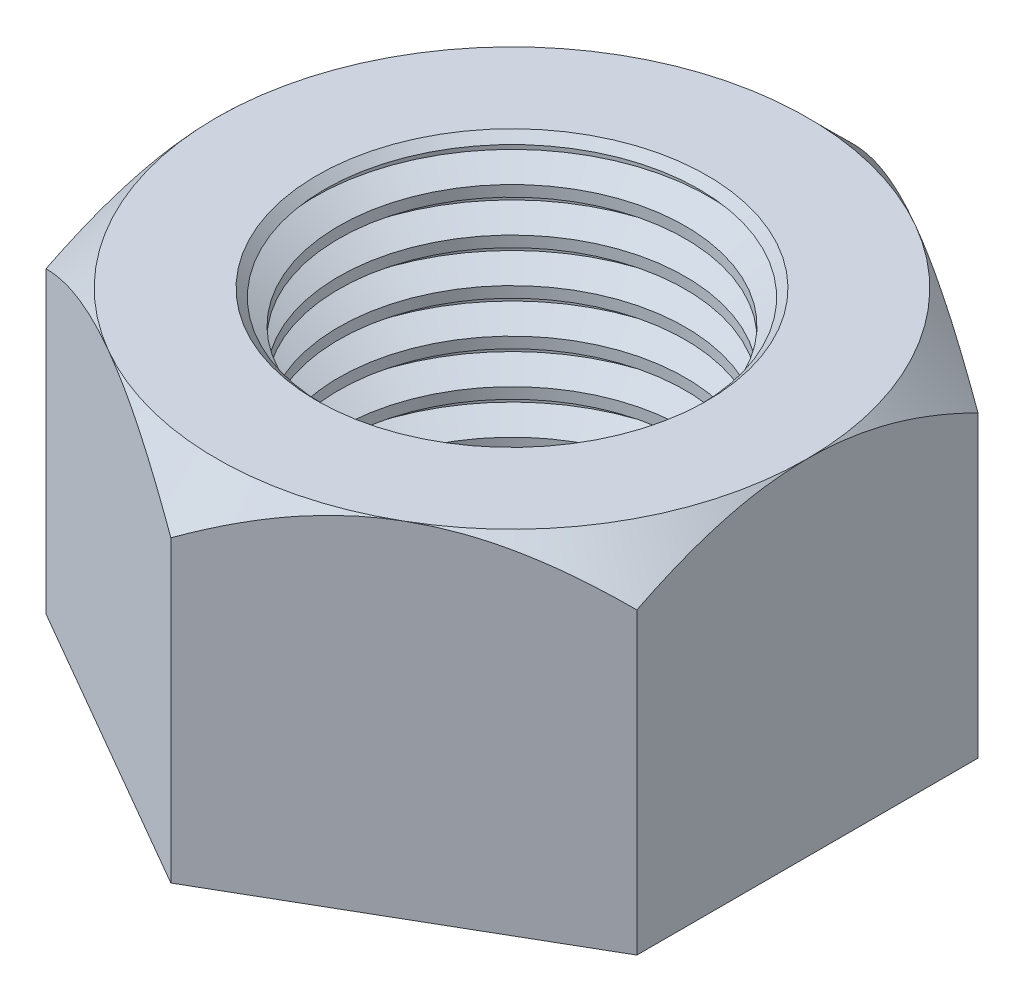
SolidWorks part; units mm, degrees
material "Alloy Steel"
ref_plane "Front" through (0, 0, 0) normal (0, 0, 1) x (1, 0, 0)
ref_plane "Top" through (0, 0, 0) normal (0, 1, 0) x (1, 0, 0)
ref_plane "Right" through (0, 0, 0) normal (1, 0, 0) x (0, 0, -1)
sketch "Sketch1" plane through (0, 0, 0) normal (0, 1, 0) x (1, 0, 0)
  line L1 (0, 8.2489) -> (-7.1438, 4.1244)
  line L2 (-7.1438, 4.1244) -> (-7.1438, -4.1244)
  line L3 (-7.1438, -4.1244) -> (0, -8.2489)
  line L4 (0, -8.2489) -> (7.1437, -4.1244)
  line L5 (7.1437, -4.1244) -> (7.1437, 4.1244)
  line L6 (7.1437, 4.1244) -> (0, 8.2489)
  circle A0 centre (0, 0) radius 7.1438 construction
  dimension "Hex Flats" = 14.2875
extrude "Extrude1" add sketch "Sketch1" along normal blind 8.3344
sketch "Sketch3" plane through (0, 0, 0) normal (1, 0, 0) x (0, 0, -1)
  line L0 (7.1437, 8.3344) -> (8.2489, 7.2292)
  line L1 (4.1244, 8.3344) -> (8.2489, 8.3344) construction
  line L2 (8.2489, 8.3344) -> (8.2489, 0) construction
  line L3 (8.2489, 7.2292) -> (8.2489, 8.3344)
  line L4 (8.2489, 8.3344) -> (7.1437, 8.3344)
  line L5 (0, 0.542) -> (0, -0.542) construction
  dimension "D1" = 45
  dimension "D2" = 14.2875
revolve "Cut-Revolve2" cut sketch "Sketch3" angle 360 about L5
sketch "Sketch2" plane through (0, 0, 0) normal (0, 0, 1) x (1, 0, 0)
  line L0 (0, 1.6636) -> (0, -0.3796) construction
  line L1 (0, 8.3344) -> (4.1897, 8.3344)
  line L3 (0, 8.3344) -> (7.1437, 8.3344) construction
  line L4 (0, 7.276) -> (4.1897, 7.276)
  line L5 (4.1897, 8.3344) -> (4.7625, 8.0036)
  line L6 (4.7625, 8.0036) -> (4.7625, 7.8714)
  line L7 (4.7625, 7.8714) -> (4.1897, 7.5406)
  line L9 (4.1897, 7.276) -> (4.1897, 7.5406)
  line L10 (0, 7.276) -> (0, 8.3344)
  line L11 (4.1897, 8.3344) -> (4.1897, 7.5406) construction
  line L12 (4.7625, 7.9375) -> (4.1897, 7.9375) construction
  dimension "D1" = 60
  dimension "D2" = 0.2646
  dimension "D5" = 0.1323
  dimension "Pitch" = 1.0583
  dimension "Major Dia." = 9.525
revolve "Cut-Revolve1" cut sketch "Sketch2" angle 360 about L0
pattern_linear "LPattern2" count 8 spacing 1.0583 along (0, -1, 0) of "Cut-Revolve1"
chamfer "Chamfer1" distance 0.5292 angle 45 1 edges at (0, 8.3344, 4.1897) first distance on face at (0, 8.3344, 0)
equation "\"D5@Sketch2\"=\"Pitch@Sketch2\"/8"
equation "\"D2@Sketch2\"=\"Pitch@Sketch2\"/4"
equation "\"D3@LPattern2\"=\"Pitch@Sketch2\""
equation "\"D1@LPattern2\"=int(\"Height@Extrude1\"/\"Pitch@Sketch2\")+1"
equation "\"D2@Sketch3\"=\"Hex Flats@Sketch1\""
equation "\"D1@Chamfer1\"=\"Pitch@Sketch2\"/2"
